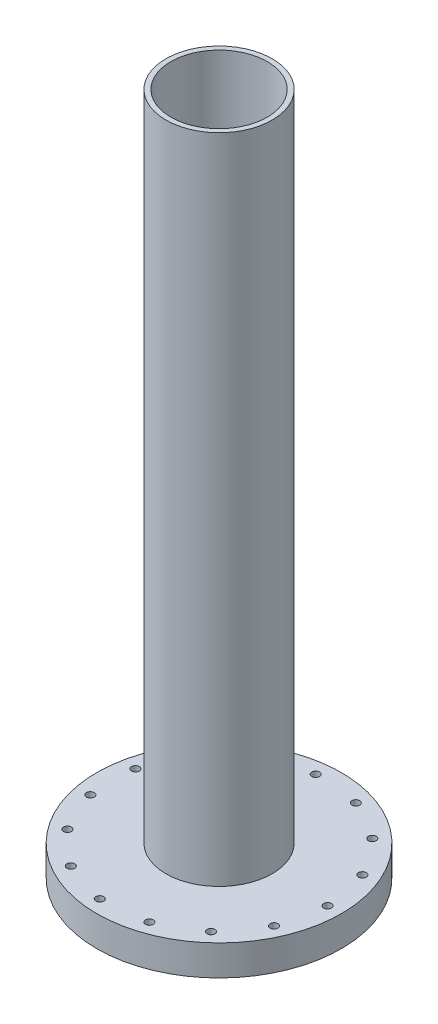
SolidWorks part; units mm, degrees
ref_plane "Front Plane" through (0, 0, 0) normal (0, 0, 1) x (1, 0, 0)
ref_plane "Top Plane" through (0, 0, 0) normal (0, 1, 0) x (1, 0, 0)
ref_plane "Right Plane" through (0, 0, 0) normal (1, 0, 0) x (0, 0, -1)
sketch "Sketch1" plane through (0, 0, 0) normal (0, 1, 0) x (1, 0, 0)
  circle A0 centre (0, 0) radius 31.75
  circle A1 centre (0, 0) radius 35
  dimension "D1" = 63.5
  dimension "D2" = 70
extrude "Boss-Extrude1" add sketch "Sketch1" along normal blind 450
sketch "Sketch2" plane through (0, 0, 0) normal (0, 1, 0) x (1, 0, 0)
  circle A0 centre (0, 0) radius 80.54
  circle A1 centre (0, 0) radius 31.75
  circle A2 centre (0, 0) radius 31.75 construction
  dimension "D1" = 161.08
extrude "Boss-Extrude2" add sketch "Sketch2" along normal blind 20
sketch "Sketch3" plane through (0, 0, 0) normal (0, -1, 0) x (1, 0, 0)
  point P0 (71.5, 0)
  point P1 (0, 0)
  dimension "D1" = 71.5
hole_wizard "13/64 (0.20313) Diameter Hole1" positions "Sketch4" profile "Sketch5" hole size "13/64" standard "ANSI Inch" end condition through all
sketch "Sketch4" plane through (0, 0, 0) normal (0, -1, 0) x (-1, 0, 0)
  point P0 (-71.5, 0)
sketch "Sketch5" plane through (71.5, 0, 0) normal (1, 0, 0) x (0, 0, -1)
  line L0 (0, 0) -> (0, 450)
  line L1 (0, 450) -> (2.5798, 450)
  line L2 (2.5798, 450) -> (2.5798, 0)
  line L5 (2.5798, 0) -> (0, 0)
  line L11 (0, -6.35) -> (0, 107.95) construction
  dimension "Thru Hole Dia." = 5.1595
  dimension "Thru Hole Depth" = 450
ref_axis "Axis1" through (0, 472.5, 0) along (0, -1, 0)
pattern_circular "CirPattern1" count 15 over 360 about axis through (0, 472.5, 0) along (0, -1, 0) of "13/64 (0.20313) Diameter Hole1"
